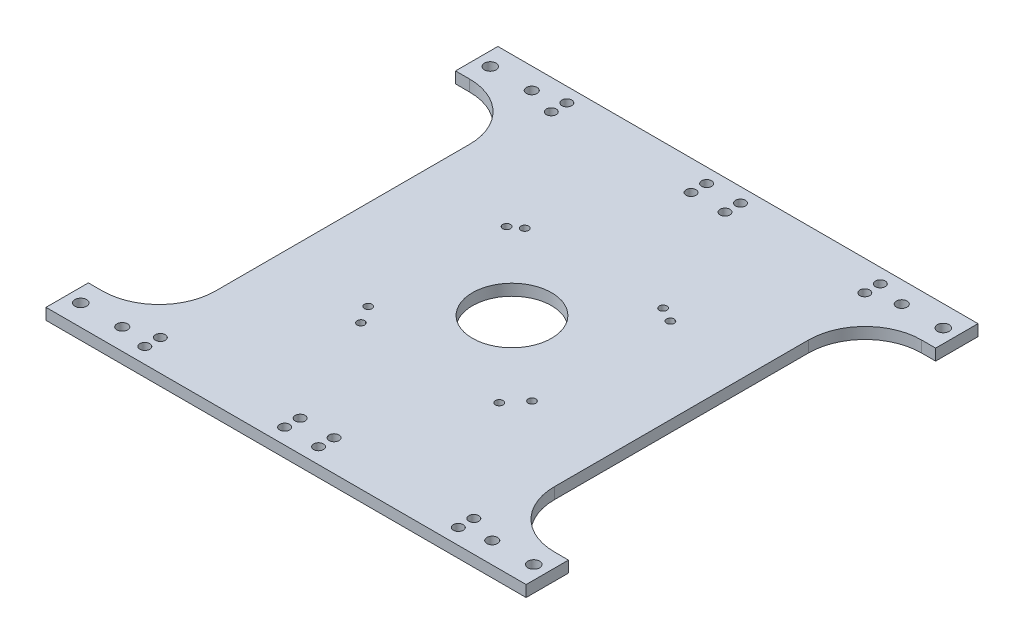
SolidWorks part; units mm, degrees
ref_plane "Front Plane" through (0, 0, 0) normal (0, 0, 1) x (1, 0, 0)
ref_plane "Top Plane" through (0, 0, 0) normal (0, 1, 0) x (1, 0, 0)
ref_plane "Right Plane" through (0, 0, 0) normal (1, 0, 0) x (0, 0, -1)
sketch "Sketch2" plane through (0, 0, 0) normal (0, 1, 0) x (1, 0, 0)
  line L0 (-60, 80) -> (60, 80)
  line L1 (-60, 80) -> (-60, -80)
  line L2 (-60, -80) -> (60, -80)
  line L3 (60, 80) -> (60, -80)
  line L4 (-60, 80) -> (60, -80) construction
  line L5 (60, 80) -> (-60, -80) construction
  line L6 (-28.2281, 26.3058) -> (-24.5, 29)
  line L7 (-24.5, 29) -> (24.5, 29)
  line L8 (24.5, 29) -> (29.7719, 26.3058)
  line L9 (29.7719, 26.3058) -> (29.7719, -22.6942)
  line L10 (29.7719, -22.6942) -> (24.5, -29)
  line L11 (24.5, -29) -> (-24.5, -29)
  line L12 (-24.5, -29) -> (-28.2281, -22.6942)
  line L13 (-28.2281, -22.6942) -> (-28.2281, 26.3058)
  line L14 (-24.5, 29) -> (0, 0)
  line L15 (0, 0) -> (24.5, -29)
  circle A0 centre (0, 0) radius 14.0022
  circle A1 centre (-28.2281, -22.6942) radius 1.35
  circle A2 centre (-24.5, -29) radius 1.35
  circle A3 centre (24.5, -29) radius 1.35
  circle A4 centre (29.7719, -22.6942) radius 1.35
  circle A5 centre (29.7719, 26.3058) radius 1.35
  circle A6 centre (24.5, 29) radius 1.35
  circle A7 centre (-28.2281, 26.3058) radius 1.35
  circle A8 centre (-24.5, 29) radius 1.35
  point P4 (0, 0)
  dimension "D3" = 2.7
  dimension "D4" = 2.7
  dimension "D5" = 2.7
  dimension "D6" = 2.7
  dimension "D7" = 2.7
  dimension "D8" = 2.7
  dimension "D9" = 2.7
  dimension "D10" = 2.7
  dimension "D11" = 28.0043
  dimension "D1" = 160
  dimension "D2" = 120
  dimension "D12" = 49
  dimension "D13" = 29
  dimension "D14" = 29
  dimension "D15" = 29.7719
  dimension "D16" = 28.2281
extrude "Boss-Extrude1" add sketch "Sketch2" along normal blind 4 contours L3 L0 L1 L2 A8 L7 A6 L8 A5 L9 A4 L10 A3 L11 A2 L12 A1 L13 A7 L6 | A8 L6 A7 L13 A1 L12 A2 L11 A3 L15 A0 L14 | A8 L14 A0 L15 A3 L10 A4 L9 A5 L8 A6 L7 region at (0, 0, -78) region at (-11.7108, 0, 9.467) region at (12.7291, 0, -9.195)
sketch "Sketch4" plane through (0, 4, 0) normal (0, 1, 0) x (1, 0, 0)
  circle A16 centre (-6, 74.9109) radius 1.75
  circle A17 centre (-6, 69.4109) radius 1.75
  circle A18 centre (-55.5, 69.4109) radius 1.75
  circle A19 centre (-55.5, 74.9109) radius 1.75
  circle A20 centre (55.5, 74.9109) radius 1.75
  circle A21 centre (55.5, 69.4109) radius 1.75
  circle A22 centre (6, 69.4109) radius 1.75
  circle A23 centre (6, 74.9109) radius 1.75
  circle A24 centre (-6, -69) radius 1.75
  circle A25 centre (-6, -74.5) radius 1.75
  circle A26 centre (-55.5, -74.5) radius 1.75
  circle A27 centre (-55.5, -69) radius 1.75
  circle A28 centre (55.5, -69) radius 1.75
  circle A29 centre (55.5, -74.5) radius 1.75
  circle A30 centre (6, -74.5) radius 1.75
  circle A31 centre (6, -69) radius 1.75
  dimension "D9" = 5.5
  dimension "D18" = 3.5
  dimension "D19" = 3.5
  dimension "D20" = 3.5
  dimension "D15" = 3.5
  dimension "D22" = 3.5
  dimension "D23" = 3.5
  dimension "D24" = 3.5
  dimension "D39" = 3.5
  dimension "D46" = 3.5
  dimension "D47" = 3.5
  dimension "D48" = 3.5
  dimension "D17" = 3.5
  dimension "D59" = 3.5
  dimension "D60" = 3.5
  dimension "D61" = 3.5
  dimension "D62" = 3.5
  dimension "D13" = 5.5
  dimension "D14" = 5.5
  dimension "D16" = 5.5
  dimension "D37" = 5.5
  dimension "D38" = 5.5
  dimension "D57" = 5.5
  dimension "D58" = 5.5
extrude "Cut-Extrude1" cut sketch "Sketch4" against normal blind 4
sketch "Sketch6" plane through (0, 4, 0) normal (0, 1, 0) x (1, 0, 0)
  line L0 (60, 45) -> (60, 65)
  line L1 (60, 80) -> (85, 80)
  line L2 (60, 80) -> (60, 65)
  line L3 (80, 65) -> (85, 65)
  line L4 (85, 80) -> (85, 65)
  line L5 (60, 80) -> (60, -80) construction
  line L6 (0, 0) -> (0, 80) construction
  line L7 (-60, 80) -> (60, 80) construction
  line L8 (-85, 80) -> (-85, 65)
  line L9 (-80, 65) -> (-85, 65)
  line L10 (-60, 80) -> (-85, 80)
  line L11 (-60, 80) -> (-60, 45)
  line L12 (-60, 0) -> (60, 0) construction
  line L13 (-60, 80) -> (-60, -80) construction
  line L14 (85, -80) -> (85, -65)
  line L15 (80, -65) -> (85, -65)
  line L16 (60, -80) -> (85, -80)
  line L17 (60, -45) -> (60, -65)
  line L18 (60, -80) -> (60, -65)
  line L19 (-60, -80) -> (-60, -45)
  line L20 (-60, -80) -> (-85, -80)
  line L21 (-80, -65) -> (-85, -65)
  line L22 (-85, -80) -> (-85, -65)
  line L23 (-60, -80) -> (60, -80) construction
  arc A0 (80, 65) -> (60, 45) centre (80, 45) ccw
  arc A1 (-80, 65) -> (-60, 45) centre (-80, 45) cw
  arc A2 (80, -65) -> (60, -45) centre (80, -45) cw
  arc A3 (-80, -65) -> (-60, -45) centre (-80, -45) ccw
  circle A4 centre (-80.2, 72.5) radius 2.0751
  circle A5 centre (-65.5, 72.5) radius 1.8895
  circle A6 centre (80.2, 72.5) radius 2.0751
  circle A7 centre (65.5, 72.5) radius 1.8895
  circle A8 centre (65.5, -72.5) radius 1.8895
  circle A9 centre (80.2, -72.5) radius 2.0751
  circle A10 centre (-65.5, -72.5) radius 1.8895
  circle A11 centre (-80.2, -72.5) radius 2.0751
  point P49 (-85, 72.5)
  dimension "D3" = 20
  dimension "D1" = 15
  dimension "D2" = 25
  dimension "D4" = 14.7
  dimension "D5" = 5.5
extrude "Boss-Extrude2" add sketch "Sketch6" against normal blind 4 separate body
combine bodies "Combine1" operation type add bodies to combine 104 102 103 105 106
